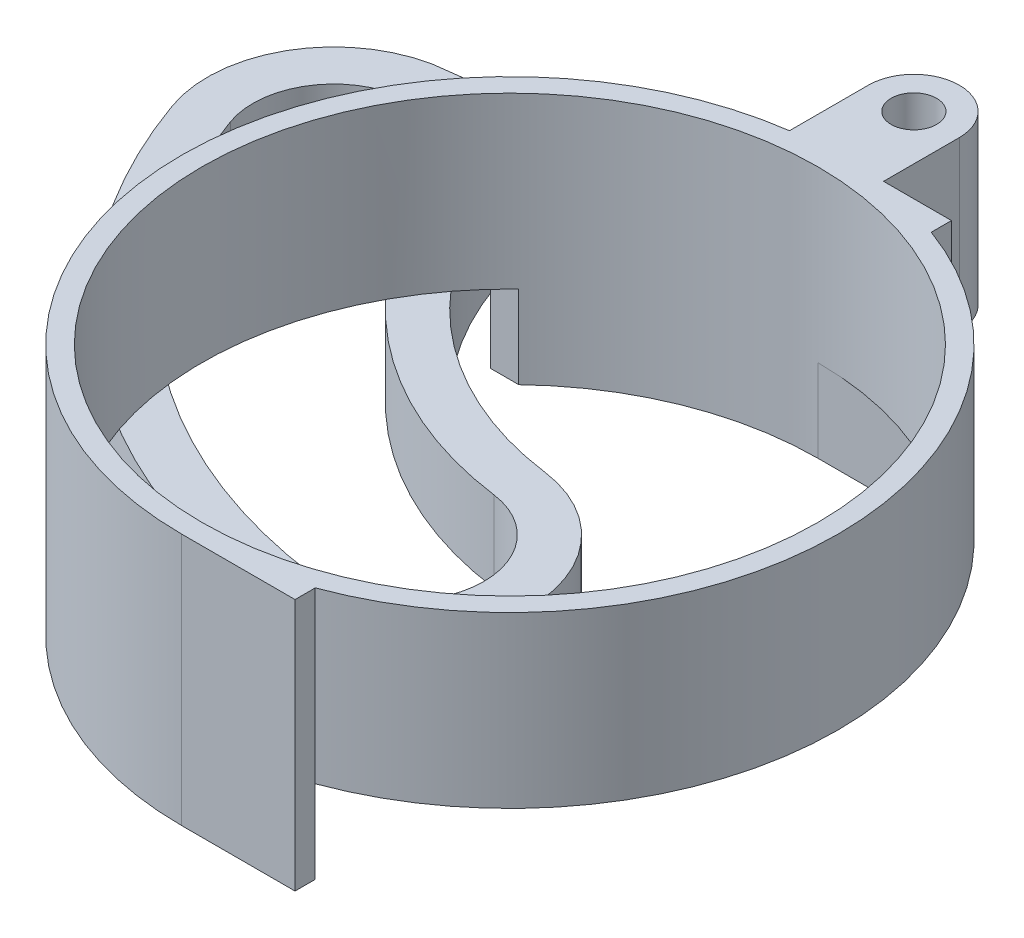
SolidWorks part; units mm, degrees
ref_plane "Front Plane" through (0, 0, 0) normal (0, 0, 1) x (1, 0, 0)
ref_plane "Top Plane" through (0, 0, 0) normal (0, 1, 0) x (1, 0, 0)
ref_plane "Right Plane" through (0, 0, 0) normal (1, 0, 0) x (0, 0, -1)
sketch "Sketch1" plane through (0, 0, 0) normal (0, 1, 0) x (1, 0, 0)
  circle A0 centre (0, 0) radius 30.5
  circle A1 centre (0, 0) radius 32.5
  dimension "D1" = 2
  dimension "D2" = 61
extrude "Boss-Extrude1" add sketch "Sketch1" along normal blind 25
sketch "Sketch2" plane through (0, 0, 0) normal (0, 1, 0) x (1, 0, 0)
  line L0 (0, -12) -> (0, -30.5)
  line L1 (0, 30.5) -> (38.6387, 30.5)
  line L2 (0, 30.5) -> (0, 22)
  line L3 (0, -30.5) -> (38.6387, -30.5)
  line L4 (38.6387, 30.5) -> (38.6387, -30.5)
  line L5 (0, -12) -> (-36.2042, -12)
  line L7 (0, 22) -> (-36.2042, 22)
  line L8 (-36.2042, -12) -> (-36.2042, 22)
  line L9 (0, 22) -> (0, -12) construction
  circle A0 centre (0, 0) radius 30.5 construction
  point P6 (0, 0)
  point P12 (0, 0)
  point P13 (0, 0)
  dimension "D1" = 22
  dimension "D2" = 12
extrude "Cut-Extrude1" cut sketch "Sketch2" along normal blind 8.2
sketch "Sketch3" plane through (0, 0, 0) normal (0, 1, 0) x (1, 0, 0)
  line L0 (0, 0) -> (0, 40) construction
  line L1 (0, 40) -> (-44.628, 34.2257) construction
  line L2 (0.385, 37.0248) -> (-32.6356, 32.7523)
  line L3 (-0.385, 42.9752) -> (-44.9137, 37.2137)
  line L4 (-5.973, -4.6018) -> (0, 40) construction
  line L5 (0, 0) -> (0, -5) construction
  arc A0 (0.385, 37.0248) -> (-0.385, 42.9752) centre (0, 40) ccw
  arc A2 (-5.973, -4.6018) -> (-42.4144, 24.9661) centre (0, 40) cw construction
  arc A3 (-54.1962, 20.79) -> (-7.6321, -16.9912) centre (0, 40) ccw
  arc A4 (-30.6326, 29.1422) -> (-4.3138, 7.7876) centre (0, 40) ccw
  arc A5 (-30.6326, 29.1422) -> (-32.6356, 32.7523) centre (-42.4144, 24.9661) ccw
  arc A6 (-7.6321, -16.9912) -> (-4.3138, 7.7876) centre (-5.973, -4.6018) ccw
  arc A7 (-44.9137, 37.2137) -> (-54.1962, 20.79) centre (-42.4144, 24.9661) ccw
  arc A8 (-5.973, -4.6018) -> (-42.4144, 24.9661) centre (0, 40) cw construction
  arc A9 (-49.9547, 22.2934) -> (-7.0348, -12.531) centre (0, 40) ccw
  arc A10 (-34.8741, 27.6388) -> (-4.9111, 3.3274) centre (0, 40) ccw
  arc A11 (-34.8741, 27.6388) -> (-49.9547, 22.2934) centre (-42.4144, 24.9661) ccw
  arc A12 (-7.0348, -12.531) -> (-4.9111, 3.3274) centre (-5.973, -4.6018) ccw
  point P0 (0, 40)
  point P2 (-28.3531, 5.0558)
  point P4 (-25.2305, 40.6952)
  point P13 (-36.7687, 7.6107)
  point P23 (0, 0)
  point P24 (0, 0)
  dimension "D2" = 25
  dimension "D3" = 5
  dimension "D6" = 12.5
  dimension "D7" = 3
  dimension "D8" = 8
  dimension "D1" = 75
  dimension "D4" = 40
  dimension "D5" = 6
extrude "Boss-Extrude2" add sketch "Sketch3" along normal blind 8 separate body
fillet "Fillet1" radius 2 1 edges at (-32.6356, 4, -32.7523)
sketch "Sketch4" plane through (0, 8, 0) normal (0, 1, 0) x (1, 0, 0)
  circle A0 centre (0, 40) radius 2
  arc A1 (0.385, 37.0248) -> (-0.385, 42.9752) centre (0, 40) ccw construction
  dimension "D1" = 4
extrude "Boss-Extrude3" add sketch "Sketch4" along normal blind 8
chamfer "Chamfer1" distance 1 angle 45 1 edges at (0, 16, -38)
sketch "Sketch5" plane through (0, 25, 0) normal (0, 1, 0) x (1, 0, 0)
  line L0 (-4.5, 40) -> (-4.5, 32.187)
  line L1 (4.5, 40) -> (4.5, 32.187)
  circle A0 centre (0, 40) radius 2.25
  circle A1 centre (0, 0) radius 32.5 construction
  arc A2 (0.385, 37.0248) -> (-0.385, 42.9752) centre (0, 40) ccw construction
  arc A3 (4.5, 40) -> (-4.5, 40) centre (0, 40) ccw
  arc A4 (4.5, 32.187) -> (-4.5, 32.187) centre (0, 0) ccw
  dimension "D1" = 4.5
  dimension "D2" = 9
extrude "Boss-Extrude4" add sketch "Sketch5" against normal offset from surface (16.6 mm away) 0.4 up to face at (0, 8, -38)
sketch "Sketch6" plane through (0, 0, 0) normal (0, -1, 0) x (1, 0, 0)
  line L1 (0, -30.5) -> (11.225, -30.5)
  line L2 (0, -30.5) -> (0, -32.5)
  line L3 (0, -32.5) -> (11.225, -32.5)
  line L4 (11.225, -30.5) -> (11.225, -32.5)
  arc A0 (-23.9217, -22) -> (11.225, -30.5) centre (0, 0) ccw construction
extrude "Boss-Extrude5" add sketch "Sketch6" against normal up to surface (25 mm away) up to face at (0, 25, -21.0467)
mirror "Mirror1" about plane through (0, 0, 0) normal (0, 0, 1) of "Boss-Extrude5"
